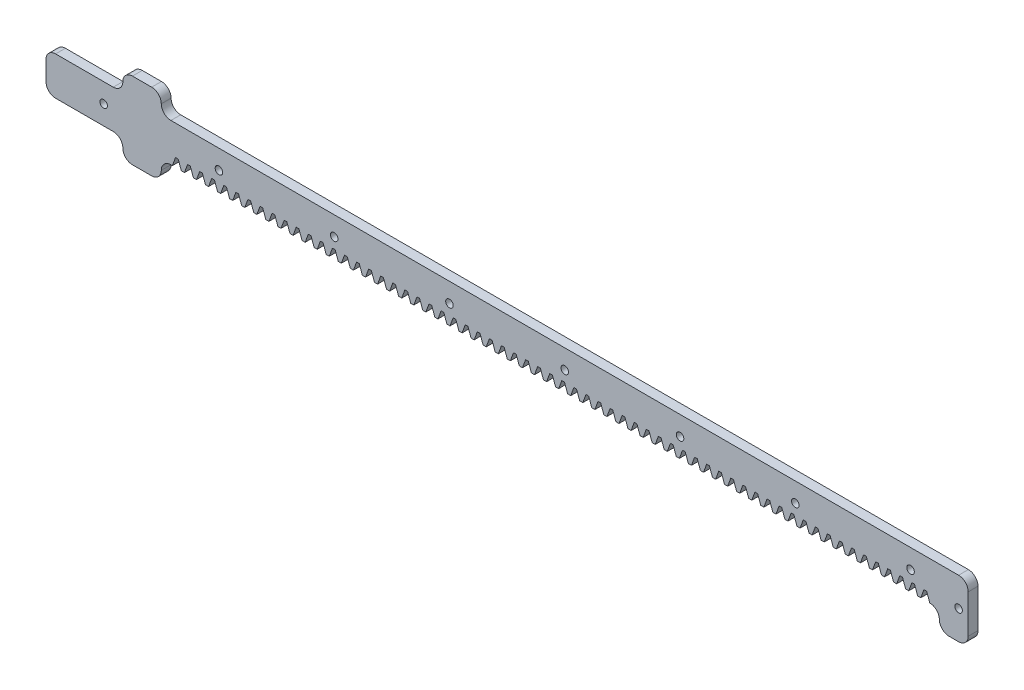
SolidWorks part; units mm, degrees
material "PC High Viscosity"
ref_plane "Front Plane" through (0, 0, 0) normal (0, 0, 1) x (1, 0, 0)
ref_plane "Top Plane" through (0, 0, 0) normal (0, 1, 0) x (1, 0, 0)
ref_plane "Right Plane" through (0, 0, 0) normal (1, 0, 0) x (0, 0, -1)
sketch "Sketch1" plane through (0, 0, 0) normal (0, 0, 1) x (1, 0, 0)
  line L0 (50.8, 0) -> (50.8, -12.7)
  line L1 (0, 0) -> (590.55, 0)
  line L2 (0, 0) -> (0, 25.4)
  line L3 (0, 25.4) -> (609.6, 25.4)
  line L4 (609.6, 0) -> (609.6, 25.4)
  line L5 (50.8, 38.1) -> (76.2, 38.1)
  line L6 (76.2, 38.1) -> (76.2, 25.4)
  line L7 (50.8, 38.1) -> (50.8, 25.4)
  line L8 (76.2, 0) -> (76.2, -12.7)
  line L9 (76.2, -12.7) -> (50.8, -12.7)
  line L10 (590.55, 0) -> (590.55, -12.7)
  line L11 (609.6, 10.0162) -> (603.25, 13.6823) construction
  line L12 (603.25, 13.6823) -> (596.9, 10.0162) construction
  line L13 (596.9, 10.0162) -> (596.9, 2.6838) construction
  line L14 (596.9, 2.6838) -> (603.25, -0.9823) construction
  line L15 (603.25, -0.9823) -> (609.6, 2.6838) construction
  line L16 (609.6, 2.6838) -> (609.6, 10.0162) construction
  line L17 (609.6, 0) -> (609.6, -12.7)
  line L18 (609.6, -12.7) -> (590.55, -12.7)
  line L19 (590.55, 0) -> (590.55, 10.0162) construction
  line L20 (590.55, 10.0162) -> (76.2, 10.0162) construction
  line L21 (76.2, 10.0162) -> (76.2, 0) construction
  circle A0 centre (603.25, 6.35) radius 2.4892
  circle A1 centre (603.25, 6.35) radius 6.35 construction
  dimension "D5" = 4.9784
  dimension "D6" = 12.7
  dimension "D7" = 12.7
  dimension "D1" = 609.6
  dimension "D2" = 25.4
  dimension "D3" = 25.4
  dimension "D4" = 514.35
  dimension "D8" = 19.05
  dimension "D9" = 12.7
extrude "Boss-Extrude1" add sketch "Sketch1" along normal blind 6.477 contours L6 L5 L3 | L1 L4 L3 L2 A0 | L9 L8 L1 region at (63.5, -6.35, 0) region at (308.9784, 12.4144, 0) region at (63.5, 31.75, 0)
fillet "Fillet2" radius 6.35 14 edges at (76.2, 38.1, 3.2385) (76.2, 25.4, 3.2385) (609.6, 25.4, 3.2385) (76.2, 0, 3.2385) (76.2, -12.7, 3.2385) (50.8, -12.7, 3.2385) (50.8, 0, 3.2385) (0, 0, 3.2385) (50.8, 38.1, 3.2385) (50.8, 25.4, 3.2385) (0, 25.4, 3.2385) (590.55, 0, 3.2385) (590.55, -12.7, 3.2385) (609.6, -12.7, 3.2385)
sketch "Sketch2" plane through (0, 0, 6.477) normal (0, 0, 1) x (1, 0, 0)
  line L0 (584.2, 0) -> (82.55, 0)
  line L1 (82.55, 0) -> (82.55, 5.715)
  line L2 (82.55, 5.715) -> (584.2, 5.715)
  line L3 (584.2, 5.715) -> (584.2, 0)
  line L5 (583.2755, 2.54) -> (575.111, 2.54) construction
  line L6 (584.2, 0) -> (582.1199, 5.715)
  line L7 (82.55, 0) -> (584.2, 0) construction
  line L8 (578.2688, 0) -> (584.2, 0)
  line L9 (579.389, 0) -> (584.2, 0)
  line L10 (582.1199, 5.715) -> (580.3488, 5.715)
  line L11 (584.2, 0) -> (578.2688, 0)
  line L12 (578.2688, 0) -> (580.3488, 5.715)
  line L13 (580.3488, 5.715) -> (582.1199, 5.715)
  line L14 (584.2, 0) -> (578.2688, 0)
  line L15 (580.3488, 5.715) -> (582.1199, 5.715)
  line L16 (584.2, 0) -> (578.2688, 0)
  line L17 (578.2688, 0) -> (576.0355, 0)
  line L19 (582.1199, 5.715) -> (580.3488, 5.715) construction
  line L20 (578.2688, 0) -> (576.0355, 0) construction
  point P8 (579.1932, 2.54)
  point P16 (583.2755, 2.54)
  point P17 (575.111, 2.54)
  dimension "D1" = 70
  dimension "D2" = 2.54
  dimension "D3" = 3.175
  dimension "D4" = 70
  dimension "D5" = 1.7711
extrude "Cut-Extrude1" cut sketch "Sketch2" against normal through all contours L12 L0 L8 L6 L2 region at (581.2344, 2.343, 6.477)
pattern_linear "LPattern1" count 63 spacing 7.9796 along (-1, 0, 0) of "Cut-Extrude1"
sketch "Sketch3" plane through (0, 0, 6.477) normal (0, 0, 1) x (1, 0, 0)
  line L0 (82.55, 25.4) -> (603.25, 25.4) construction
  line L1 (609.6, 19.05) -> (609.6, -6.35) construction
  circle A0 centre (571.5, 12.7) radius 2.4892
  dimension "D2" = 4.9784
  dimension "D4" = 12.7
  dimension "D5" = 38.1
extrude "Cut-Extrude2" cut sketch "Sketch3" against normal through all
pattern_linear "LPattern2" count 8 spacing 76.2 along (-1, 0, 0) of "Cut-Extrude2"
